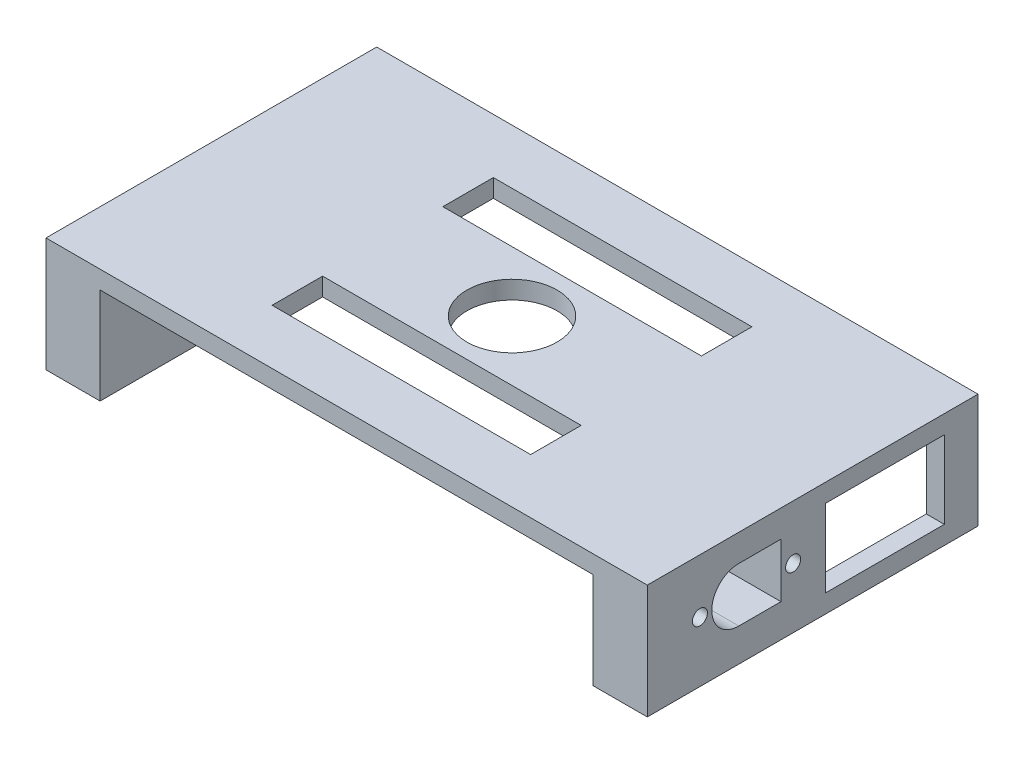
SolidWorks part; units mm, degrees
ref_plane "Front Plane" through (0, 0, 0) normal (0, 0, 1) x (1, 0, 0)
ref_plane "Top Plane" through (0, 0, 0) normal (0, 1, 0) x (1, 0, 0)
ref_plane "Right Plane" through (0, 0, 0) normal (1, 0, 0) x (0, 0, -1)
sketch "Sketch1" plane through (0, 0, 0) normal (0, 1, 0) x (1, 0, 0)
  line L1 (-50, -27.5) -> (50, -27.5)
  line L2 (-50, -27.5) -> (-50, 27.5)
  line L3 (-50, 27.5) -> (50, 27.5)
  line L4 (50, -27.5) -> (50, 27.5)
  line L5 (-50, -27.5) -> (50, 27.5) construction
  line L6 (-50, 27.5) -> (50, -27.5) construction
  point P0 (0, 0)
  dimension "D1" = 100
  dimension "D2" = 55
extrude "Boss-Extrude1" add sketch "Sketch1" along normal blind 19
sketch "Sketch2" plane through (0, 0, 0) normal (0, -1, 0) x (1, 0, 0)
  line L1 (-41, -45.5) -> (41, -45.5)
  line L2 (-41, -45.5) -> (-41, 45.5)
  line L3 (-41, 45.5) -> (41, 45.5)
  line L4 (41, -45.5) -> (41, 45.5)
  line L5 (-41, -45.5) -> (41, 45.5) construction
  line L6 (-41, 45.5) -> (41, -45.5) construction
  point P0 (0, 0)
  dimension "D1" = 91
  dimension "D2" = 82
extrude "Cut-Extrude1" cut sketch "Sketch2" against normal blind 16
sketch "Sketch3" plane through (50, 0, 0) normal (1, 0, 0) x (0, 0, -1)
  line L3 (-5.2727, 5.5) -> (-5.2727, 14.5)
  line L4 (-5.2727, 5.5) -> (-12.2784, 5.5)
  line L9 (-5.2727, 14.5) -> (-12.2784, 14.5)
  arc A1 (-12.2784, 5.5) -> (-12.2784, 14.5) centre (-12.2784, 10) cw
  circle A2 centre (-18.75, 10) radius 1.25
  circle A3 centre (-3.25, 10) radius 1.25
  point P17 (-11, 10)
extrude "Cut-Extrude3" cut sketch "Sketch3" against normal up to next
sketch "Sketch15" plane through (50, 0, 0) normal (1, 0, 0) x (0, 0, -1)
  line L0 (0, 0) -> (0, 19) construction
  line L1 (-27.5, 19) -> (27.5, 19) construction
  line L2 (0, 9.5) -> (12, 9.5) construction
  line L4 (2.1, 3.05) -> (21.9, 3.05)
  line L5 (2.1, 3.05) -> (2.1, 15.95)
  line L6 (2.1, 15.95) -> (21.9, 15.95)
  line L7 (21.9, 3.05) -> (21.9, 15.95)
  line L8 (2.1, 3.05) -> (21.9, 15.95) construction
  line L9 (2.1, 15.95) -> (21.9, 3.05) construction
  dimension "D1" = 12
  dimension "D2" = 19.8
  dimension "D3" = 12.9
extrude "Cut-Extrude13" cut sketch "Sketch15" against normal up to next
sketch "Sketch6" plane through (0, 19, 0) normal (0, 1, 0) x (1, 0, 0)
  line L0 (0, 0) -> (0, -10) construction
  line L1 (21.5, -10) -> (-21.5, -10)
  line L2 (-21.5, -10) -> (-21.5, -18.4)
  line L3 (21.5, -10) -> (21.5, -18.4)
  line L4 (21.5, -18.4) -> (-21.5, -18.4)
  line L5 (0, 0) -> (5, 0) construction
  line L6 (21.5, 10) -> (21.5, 18.4)
  line L7 (21.5, 10) -> (-21.5, 10)
  line L8 (-21.5, 10) -> (-21.5, 18.4)
  line L9 (21.5, 18.4) -> (-21.5, 18.4)
  circle A0 centre (0, 0) radius 7.5
  point P6 (0, -10)
  dimension "D5" = 15
  dimension "D1" = 10
  dimension "D2" = 43
  dimension "D3" = 8.4
  dimension "D4" = 5
extrude "Cut-Extrude14" cut sketch "Sketch6" against normal up to next
sketch "Sketch16" plane through (0, 0, 0) normal (0, -1, 0) x (1, 0, 0)
  line L1 (41, -27.5) -> (47, -27.5)
  line L2 (41, -27.5) -> (41, 0)
  line L3 (41, 0) -> (47, 0)
  line L4 (47, -27.5) -> (47, 0)
  dimension "D1" = 6
  dimension "D2" = 27.5
extrude "Cut-Extrude15" cut sketch "Sketch16" against normal blind 16
sketch "Sketch17" [suppressed] plane through (0, 0, 0) normal (0, -1, 0) x (1, 0, 0)
  line L1 (41, 27.5) -> (-50, 27.5)
  line L2 (41, 27.5) -> (41, -27.5)
  line L3 (41, -27.5) -> (-50, -27.5)
  line L4 (-50, 27.5) -> (-50, -27.5)
extrude "Cut-Extrude16" [suppressed] cut sketch "Sketch17" against normal through all
